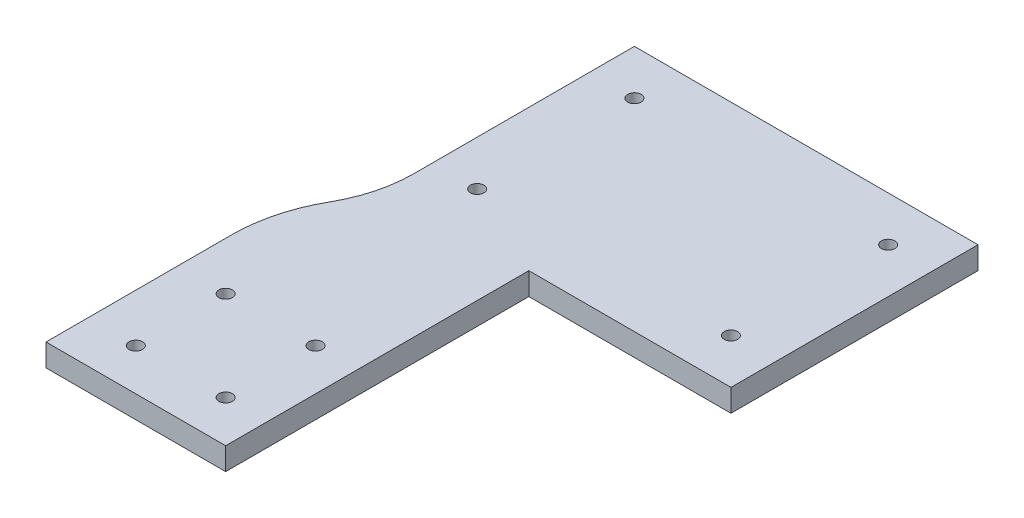
SolidWorks part; units mm, degrees
ref_plane "Front Plane" through (0, 0, 0) normal (0, 0, 1) x (1, 0, 0)
ref_plane "Top Plane" through (0, 0, 0) normal (0, 1, 0) x (1, 0, 0)
ref_plane "Right Plane" through (0, 0, 0) normal (1, 0, 0) x (0, 0, -1)
sketch "Sketch1" plane through (0, 0, 0) normal (0, 1, 0) x (1, 0, 0)
  line L14 (165, -120) -> (85, -120)
  line L22 (165, 15) -> (255, 15)
  line L23 (255, 15) -> (255, 125)
  line L25 (165, -120) -> (165, 15)
  line L26 (102, 125) -> (255, 125)
  line L31 (85, -120) -> (85, -15)
  line L32 (85, -15) -> (102, -15)
  line L33 (102, -15) -> (102, 125)
  circle A0 centre (146.4, -101.4) radius 3
  circle A1 centre (106.4, -101.4) radius 3
  circle A2 centre (146.4, -61.4) radius 3
  circle A3 centre (106.4, -61.4) radius 3
  circle A4 centre (122, 35) radius 3
  circle A5 centre (235, 35) radius 3
  circle A6 centre (235, 105) radius 3
  circle A7 centre (122, 105) radius 3
  point P22 (0, 0)
  point P25 (0, 0)
  point P26 (0, 0)
  point P27 (0, 0)
  point P28 (0, 0)
  point P29 (0, 0)
  point P30 (0, 0)
  point P31 (0, 0)
  point P32 (0, 0)
  point P33 (0, 0)
  point P34 (0, 0)
  point P35 (0, 0)
  point P36 (0, 0)
  point P37 (0, 0)
  point P38 (0, 0)
  point P39 (0, 0)
  point P40 (0, 0)
  point P41 (0, 0)
  point P42 (0, 0)
  point P43 (0, 0)
  dimension "D1" = 18.6
  dimension "D2" = 40
  dimension "D3" = 40
  dimension "D4" = 18.6
  dimension "D8" = 20
extrude "Boss-Extrude1" add sketch "Sketch1" along normal blind 10
fillet "Fillet2" radius 60 1 edges at (102, 5, 15)
fillet "Fillet3" radius 70 1 edges at (85, 5, 15)
